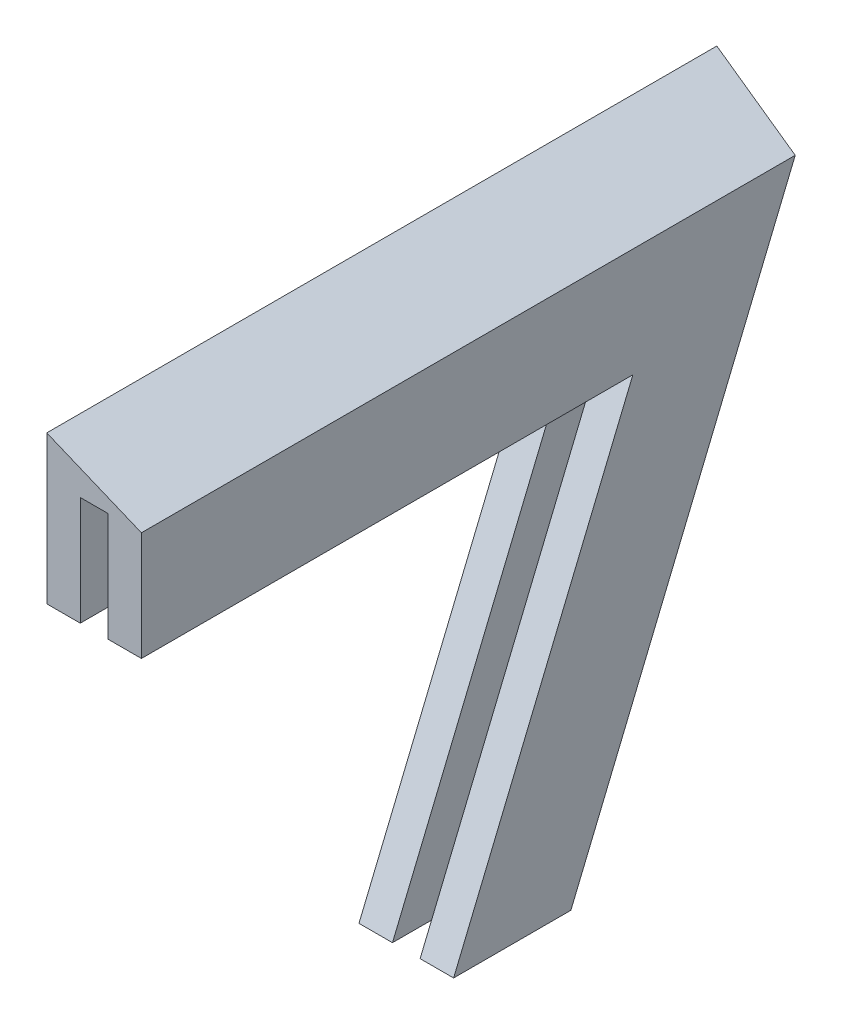
SolidWorks part; units mm, degrees
ref_plane "Front Plane" through (0, 0, 0) normal (0, 0, 1) x (1, 0, 0)
ref_plane "Top Plane" through (0, 0, 0) normal (0, 1, 0) x (1, 0, 0)
ref_plane "Right Plane" through (0, 0, 0) normal (1, 0, 0) x (0, 0, -1)
sketch "Sketch7" plane through (0, 0, 0) normal (0, 0, 1) x (1, 0, 0)
  line L0 (-1.7, -2) -> (-1.7, -15)
  line L1 (-1.7, -15) -> (-5.7, -15)
  line L2 (-5.7, -15) -> (-5.7, -2)
  line L3 (-5.7, -2) -> (-9, -2)
  line L4 (-9, -2) -> (-9, -15)
  line L5 (-9, -15) -> (-13, -15)
  line L7 (-13, -15) -> (-13, 2.6806)
  line L9 (-1.7, -2) -> (-13, 2.6806)
extrude "Boss-Extrude3" add sketch "Sketch7" along normal blind 80
sketch "Sketch11" plane through (-13, 0, 0) normal (-1, 0, 0) x (0, 0, 1)
  line L0 (0, 2.6806) -> (7.3231, -15)
  line L2 (80, -15) -> (0, -15) construction
  line L3 (7.3231, -15) -> (0, -15)
  line L4 (0, -15) -> (0, 2.6806)
extrude "Cut-Extrude1" cut sketch "Sketch11" against normal through all
sketch "Sketch22" plane through (0, -2, 0) normal (0, -1, 0) x (-1, 0, 0)
  line L0 (5.7, -1.9386) -> (5.7, -2.9386)
  line L1 (5.7, -80) -> (5.7, -1.9386) construction
  line L2 (5.7, -1.9386) -> (9, -1.9386)
  line L3 (9, -1.9386) -> (9, -2.9386)
  line L4 (9, -2.9386) -> (5.7, -2.9386)
extrude "Boss-Extrude10" add sketch "Sketch22" along direction (0, -0.9239, 0.3827) on the side of the normal up to vertex (13 mm away) up to point (-1.7, -15, 7.3231)
sketch "Sketch24" plane through (0, -15, 0) normal (0, -1, 0) x (-1, 0, 0)
  line L0 (13, -7.3231) -> (1.7, -7.3231)
  line L1 (13, -7.3231) -> (13, -21.3231)
  line L2 (13, -80) -> (13, -7.3231) construction
  line L3 (1.7, -7.3231) -> (1.7, -21.3231)
  line L4 (1.7, -80) -> (1.7, -7.3231) construction
  line L5 (9, -8.3231) -> (9, -21.3231)
  line L6 (9, -80) -> (9, -8.3231) construction
  line L7 (5.7, -8.3231) -> (5.7, -21.3231)
  line L8 (5.7, -80) -> (5.7, -8.3231) construction
  line L9 (13, -21.3231) -> (9, -21.3231)
  line L10 (9, -8.3231) -> (5.7, -8.3231)
  line L11 (5.7, -21.3231) -> (1.7, -21.3231)
extrude "Boss-Extrude11" add sketch "Sketch24" along direction (0, 0.9239, -0.3827) on the side of the normal blind 55.93
ref_plane "Plane4" through (-0.9561, -2.3081, 0) normal (0.3827, 0.9239, 0) x (0.9239, -0.3827, 0)
